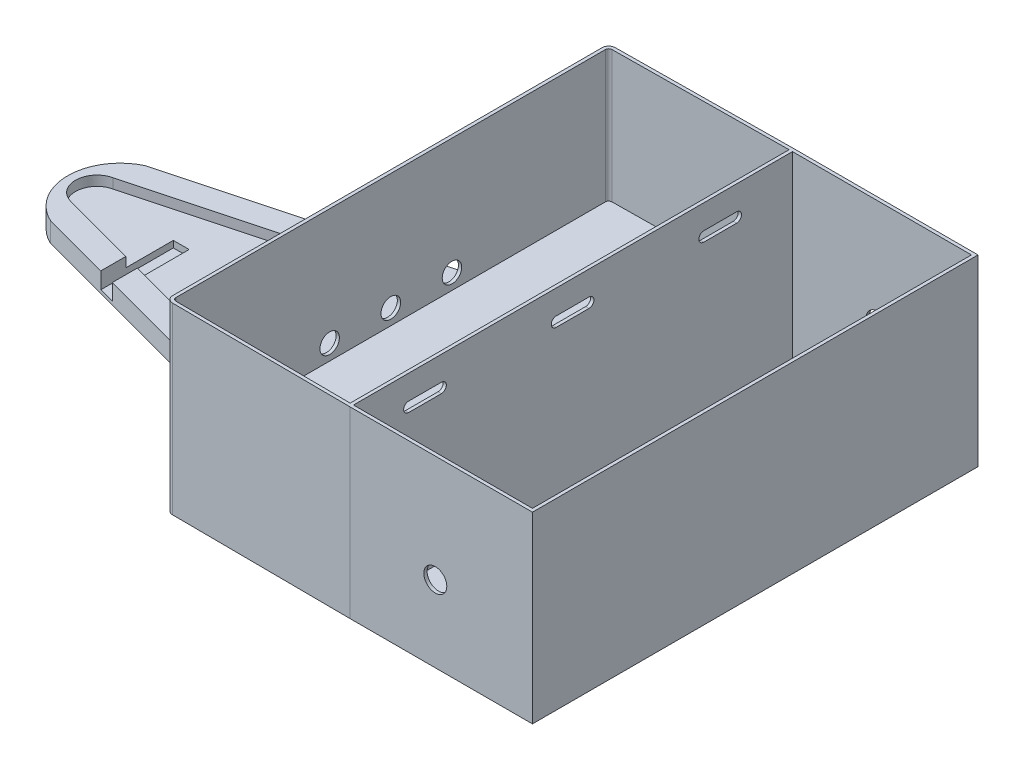
SolidWorks part; units mm, degrees
ref_plane "Front Plane" through (0, 0, 0) normal (0, 0, 1) x (1, 0, 0)
ref_plane "Top Plane" through (0, 0, 0) normal (0, 1, 0) x (1, 0, 0)
ref_plane "Right Plane" through (0, 0, 0) normal (1, 0, 0) x (0, 0, -1)
sketch "Sketch2" plane through (0, 0, 0) normal (0, 1, 0) x (1, 0, 0)
  line L0 (-46.067, 4.9945) -> (35.0073, 26.7183)
  line L1 (-46.067, -7.7557) -> (35.0073, -29.4795)
  line L2 (-44.3588, -15.8447) -> (100.5301, -54.6675)
  line L3 (-44.3588, -1.3806) -> (-29.6123, -1.3806) construction
  line L4 (-44.3588, 13.0835) -> (100.5301, 51.9063)
  line L5 (100.5301, 51.9063) -> (100.5301, -54.6675)
  arc A2 (35.0073, 26.7183) -> (35.0073, -29.4795) centre (-71.3433, -1.3806) cw
  arc A4 (-44.3588, 13.0835) -> (-44.3588, -15.8447) centre (-37.5184, -1.3806) ccw
  arc A5 (-46.067, 4.9945) -> (-46.067, -7.7557) centre (-44.6045, -1.3806) ccw
extrude "Boss-Extrude1" add sketch "Sketch2" along normal blind 3 contours A2 L0 A5 L1 | L4 A4 L2 L5 L0 A2 L1 A5 | L0 A2 L1 A5 | L4 L5 L2 A4 region at (3.6982, 0, 1.3806) region at (55.7011, 0, 1.3806)
extrude "Boss-Extrude2" add sketch "Sketch2<3>" along normal blind 6 contours L4 A4 L2 L5 L0 A2 L1 A5 region at (55.7011, 0, 1.3806)
sketch "Sketch2<3>" plane through (0, 0, 0) normal (0, 1, 0) x (1, 0, 0) same geometry as "Sketch2"
sketch "Sketch3" plane through (0, 6, 0) normal (0, 1, 0) x (1, 0, 0)
  line L0 (-44.6045, -1.3806) -> (100.5301, -1.3806) construction
  line L1 (100.5301, 51.9063) -> (100.5301, -54.6675) construction
  line L3 (-44.3588, 13.0835) -> (100.5301, 51.9063) construction
  line L4 (44.0725, -66.9672) -> (44.0725, -39.5398)
  line L5 (-44.3588, -15.8447) -> (100.5301, -54.6675) construction
  line L11 (100.5301, 66.548) -> (100.5301, 51.9063)
  line L14 (100.5301, -69.3092) -> (100.5301, -54.6675)
  line L20 (44.0725, 63.9818) -> (44.0725, 36.7786)
  line L22 (46.06, -68.9671) -> (100.5301, -69.3092)
  line L23 (46.0517, 65.9817) -> (100.5301, 66.548)
  line L24 (44.0725, 36.7786) -> (44.0725, -39.5398)
  line L25 (100.5301, 51.9063) -> (100.5301, -54.6675)
  arc A4 (46.06, -68.9671) -> (44.0725, -66.9672) centre (46.0725, -66.9672) cw
  arc A5 (44.0725, 63.9818) -> (46.0517, 65.9817) centre (46.0725, 63.9818) cw
  dimension "D3" = 2
  dimension "D4" = 2
extrude "Boss-Extrude3" add sketch "Sketch3" against normal blind 6 and the other way blind 9.69
fillet "Fillet1" radius 2 1 edges at (44.0725, 3, 39.5398)
fillet "Fillet2" radius 2 1 edges at (44.0725, 3, -36.7786)
sketch "Sketch5" plane through (0, 15.69, 0) normal (0, 1, 0) x (1, 0, 0)
  line L0 (46.06, -68.9671) -> (100.5301, -69.3092) construction
  line L1 (44.0725, 63.9818) -> (44.0725, -66.9672) construction
  line L2 (100.5301, 66.548) -> (46.0517, 65.9817) construction
  line L3 (100.5301, -69.3092) -> (100.5301, 66.548) construction
  line L4 (46.06, -68.9671) -> (100.5301, -69.3092)
  line L5 (44.0725, 63.9818) -> (44.0725, -66.9672)
  line L6 (100.5301, 66.548) -> (46.0517, 65.9817)
  line L7 (100.5301, -69.3092) -> (100.5301, 66.548)
  line L8 (99.5301, -68.3029) -> (99.5301, 65.5375)
  line L9 (99.5301, 65.5375) -> (46.0621, 64.9817)
  line L10 (45.0725, 63.9818) -> (45.0725, -66.9672)
  line L11 (46.0662, -67.9671) -> (99.5301, -68.3029)
  arc A0 (44.0725, -66.9672) -> (46.06, -68.9671) centre (46.0725, -66.9672) ccw construction
  arc A1 (46.0517, 65.9817) -> (44.0725, 63.9818) centre (46.0725, 63.9818) ccw construction
  arc A2 (44.0725, -66.9672) -> (46.06, -68.9671) centre (46.0725, -66.9672) ccw
  arc A3 (46.0517, 65.9817) -> (44.0725, 63.9818) centre (46.0725, 63.9818) ccw
  arc A4 (46.0621, 64.9817) -> (45.0725, 63.9818) centre (46.0725, 63.9818) ccw
  arc A5 (45.0725, -66.9672) -> (46.0662, -67.9671) centre (46.0725, -66.9672) ccw
  dimension "D1" = 1
extrude "Boss-Extrude4" add sketch "Sketch5" along normal offset from surface (40.2333 mm away) 1.5 offset beyond the face yes
sketch "Sketch6" plane through (44.0725, 0, 0) normal (-1, 0, 0) x (0, 0, 1)
  spline S1 degree 3 poles (-14.0187, 21.3489) (-15.586, 23.3405) (-18.1077, 23.5939) (-20.0605, 21.9978) (-20.3591, 19.4933) (-18.7918, 17.5017) (-16.2701, 17.2483) (-14.3172, 18.8445) (-14.0187, 21.3489) (-15.586, 23.3405) (-18.1077, 23.5939) knots -2.356194 -1.570796 -0.785398 0 0.785398 1.570796 2.356194 3.141593 3.926991 4.712389 5.497787 6.283185 7.068583 7.853982 8.63938 only from (-15.7451, 23.0508) to (-15.7451, 23.0508)
  spline S3 degree 3 poles (4.1376, 18.4613) (4.745, 20.9298) (3.4198, 23.0992) (0.9515, 23.6955) (-1.2212, 22.381) (-1.8286, 19.9125) (-0.5035, 17.743) (1.9649, 17.1467) (4.1376, 18.4613) (4.745, 20.9298) (3.4198, 23.0992) knots -2.356194 -1.570796 -0.785398 0 0.785398 1.570796 2.356194 3.141593 3.926991 4.712389 5.497787 6.283185 7.068583 7.853982 8.63938 only from (4.4229, 20.8799) to (4.4229, 20.8799)
  spline S5 degree 3 poles (22.4363, 22.7608) (20.1028, 23.7513) (17.7694, 22.7608) (16.824, 20.4211) (17.7694, 18.0814) (20.1028, 17.091) (22.4363, 18.0814) (23.3816, 20.4211) (22.4363, 22.7608) (20.1028, 23.7513) (17.7694, 22.7608) knots -2.356194 -1.570796 -0.785398 0 0.785398 1.570796 2.356194 3.141593 3.926991 4.712389 5.497787 6.283185 7.068583 7.853982 8.63938 only from (20.1028, 23.4211) to (20.1028, 23.4211)
extrude "Cut-Extrude1" cut sketch "Sketch6" against normal blind 1.5
sketch "Sketch7" plane through (100.5301, 0, 0) normal (1, 0, 0) x (0, 0, -1)
  line L0 (-51.4877, 47.0285) -> (-41.4927, 47.0285) construction
  line L1 (-51.4877, 48.5346) -> (-41.4927, 48.5346)
  line L2 (-51.4877, 45.5225) -> (-41.4927, 45.5225)
  line L3 (-6.4877, 47.0285) -> (3.5073, 47.0285) construction
  line L4 (-6.4877, 48.5346) -> (3.5073, 48.5346)
  line L5 (-6.4877, 45.5225) -> (3.5073, 45.5225)
  line L6 (38.5123, 47.0285) -> (48.5073, 47.0285) construction
  line L10 (-69.3092, 55.9233) -> (-69.3092, 0)
  line L11 (-69.3092, 0) -> (66.548, 0)
  line L12 (66.548, 0) -> (66.548, 55.9233)
  line L13 (66.548, 55.9233) -> (-69.3092, 55.9233)
  line L14 (-69.3092, 55.9233) -> (-69.3092, 0)
  line L15 (-69.3092, 0) -> (66.548, 0)
  line L16 (66.548, 0) -> (66.548, 55.9233)
  line L17 (66.548, 55.9233) -> (-69.3092, 55.9233)
  line L23 (38.5123, 48.5346) -> (48.5073, 48.5346)
  line L24 (38.5123, 45.5225) -> (48.5073, 45.5225)
  arc A0 (3.5073, 46.5176) -> (3.5073, 47.5394) centre (3.5073, 47.0285) ccw construction
  arc A2 (-6.4877, 46.5225) -> (-6.4877, 47.5346) centre (-6.4877, 47.0285) ccw
  arc A3 (-6.4877, 47.5346) -> (-6.4877, 46.5225) centre (-6.4877, 47.0285) ccw
  arc A4 (-6.4877, 46.5225) -> (-6.4877, 47.5346) centre (-6.4877, 47.0285) ccw
  arc A5 (-6.4877, 47.5346) -> (-6.4877, 46.5225) centre (-6.4877, 47.0285) ccw
  arc A6 (-51.4877, 48.5346) -> (-51.4877, 45.5225) centre (-51.4877, 47.0285) ccw
  arc A7 (-51.4877, 48.5346) -> (-51.4877, 45.5225) centre (-51.4877, 47.0285) ccw
  arc A8 (-51.4877, 48.5346) -> (-51.4877, 45.5225) centre (-51.4877, 47.0285) ccw
  arc A9 (-41.4927, 45.5225) -> (-41.4927, 48.5346) centre (-41.4927, 47.0285) ccw
  arc A10 (-6.4877, 48.5346) -> (-6.4877, 45.5225) centre (-6.4877, 47.0285) ccw
  arc A11 (3.5073, 45.5225) -> (3.5073, 48.5346) centre (3.5073, 47.0285) ccw
  arc A16 (38.5123, 48.5346) -> (38.5123, 45.5225) centre (38.5123, 47.0285) ccw
  arc A17 (48.5073, 45.5225) -> (48.5073, 48.5346) centre (48.5073, 47.0285) ccw
  arc A22 (38.5123, 46.5225) -> (38.5123, 47.5346) centre (38.5123, 47.0285) ccw
  arc A23 (38.5123, 47.5346) -> (38.5123, 46.5225) centre (38.5123, 47.0285) ccw
  arc A24 (38.5123, 46.5225) -> (38.5123, 47.5346) centre (38.5123, 47.0285) ccw
  arc A25 (38.5123, 47.5346) -> (38.5123, 46.5225) centre (38.5123, 47.0285) ccw
  point P0 (-46.4902, 47.0285)
  point P6 (-1.4902, 47.0285)
  point P30 (43.5098, 47.0285)
  dimension "D4" = 1
  dimension "D5" = 0.9951
  dimension "D6" = 1.5061
  dimension "D8" = 0
  dimension "D7" = 9.995
  dimension "D1" = 1
  dimension "D2" = 0
  dimension "D3" = 0
extrude "Cut-Extrude2" cut sketch "Sketch7" against normal blind 1.5 contours L1 A9 L2 A6 | L4 A11 L5 A10 | L23 A17 L24 A16
sketch "Sketch8" plane through (100.5301, 0, 0) normal (1, 0, 0) x (0, 0, -1)
  line L0 (66.548, 55.9233) -> (66.548, 0) construction
  line L1 (66.548, 0) -> (-69.3092, 0) construction
  line L2 (-69.3092, 55.9233) -> (-69.3092, 0) construction
  line L3 (66.548, 55.9233) -> (66.548, 0)
  line L4 (66.548, 0) -> (-69.3092, 0)
  line L5 (-69.3092, 55.9233) -> (-69.3092, 0)
  line L6 (-68.3092, 55.9233) -> (-68.3092, 1)
  line L7 (65.548, 1) -> (-68.3092, 1)
  line L8 (65.548, 55.9233) -> (65.548, 1)
  line L9 (-68.3092, 55.9233) -> (-69.3092, 55.9233)
  line L10 (66.548, 55.9233) -> (65.548, 55.9233)
  dimension "D1" = 1
extrude "Boss-Extrude5" add sketch "Sketch8" along normal blind 54.58
sketch "Sketch9" plane through (0, 0, 0) normal (0, -1, 0) x (-1, 0, 0)
  line L0 (53.5184, -1.3806) -> (-155.1101, -1.3806) construction
  line L1 (-155.1101, -69.3092) -> (-155.1101, 66.548) construction
  arc A0 (44.3588, -15.8447) -> (44.3588, 13.0835) centre (37.5184, -1.3806) ccw construction
sketch "Sketch10" plane through (0, 0, -65.548) normal (0, 0, 1) x (1, 0, 0)
  line L0 (132.9683, 11.5372) -> (120.0143, 11.5372) construction
  line L1 (132.9683, 11.5372) -> (120.0143, 11.5372)
  circle A0 centre (126.4913, 23.2467) radius 3.5
  point P5 (126.4913, 11.5372)
  dimension "D1" = 7
extrude "Cut-Extrude3" cut sketch "Sketch10" against normal through all both and the other way through all contours A0
sketch "Sketch12" plane through (0, 6, 0) normal (0, 1, 0) x (1, 0, 0)
  line L4 (7.9822, -41.7058) -> (19.9822, -41.7058)
  line L5 (7.9822, -41.7058) -> (7.9822, -10.9795)
  line L6 (7.9822, -10.9795) -> (19.9822, -10.9795)
  line L7 (19.9822, -41.7058) -> (19.9822, -10.9795)
  line L8 (-18.5059, -29.5962) -> (-23.3344, -29.5962)
  line L9 (-18.5059, -29.5962) -> (-18.5059, 0.6354)
  line L10 (-18.5059, 0.6354) -> (-23.3344, 0.6354)
  line L11 (-23.3344, -29.5962) -> (-23.3344, 0.6354)
  dimension "D1" = 12
extrude "Cut-Extrude4" cut sketch "Sketch12" against normal blind 5
sketch "Sketch13" plane through (155.1101, 0, 0) normal (1, 0, 0) x (0, 0, -1)
  line L1 (-69.3092, 55.9233) -> (66.548, 55.9233)
  line L2 (-69.3092, 55.9233) -> (-69.3092, 0)
  line L3 (-69.3092, 0) -> (66.548, 0)
  line L4 (66.548, 55.9233) -> (66.548, 0)
extrude "Boss-Extrude6" add sketch "Sketch13" along normal blind 1
